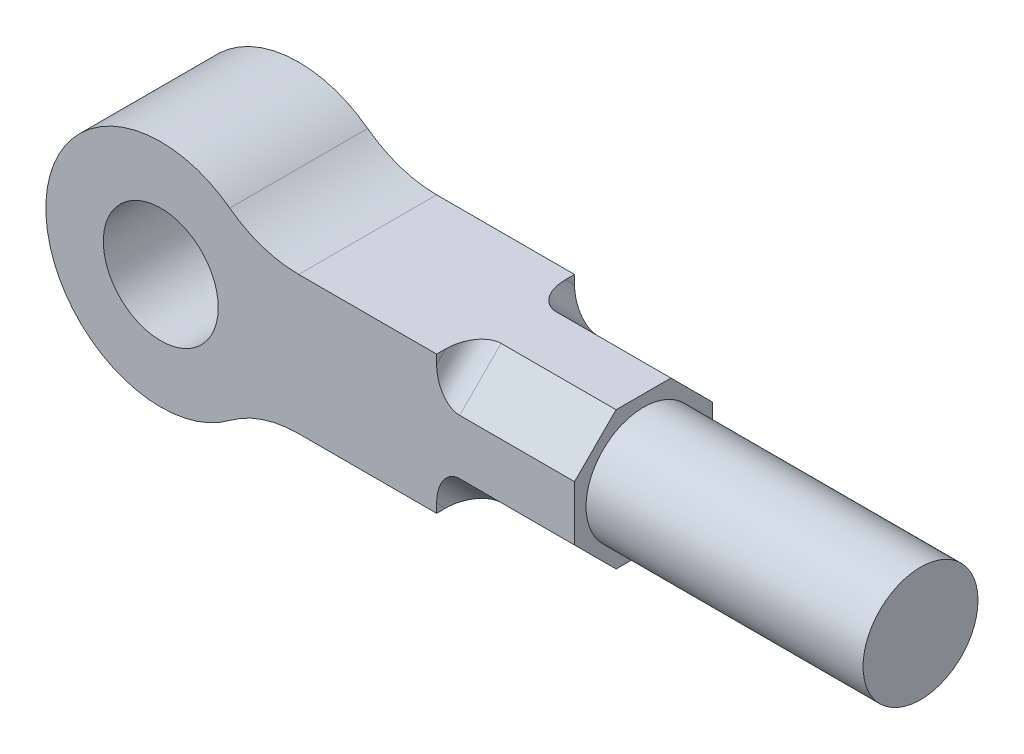
SolidWorks part; units mm, degrees
ref_plane "Front Plane" through (0, 0, 0) normal (0, 0, 1) x (1, 0, 0)
ref_plane "Top Plane" through (0, 0, 0) normal (0, 1, 0) x (1, 0, 0)
ref_plane "Right Plane" through (0, 0, 0) normal (1, 0, 0) x (0, 0, -1)
sketch "Sketch1" plane through (0, 0, 0) normal (0, 0, 1) x (1, 0, 0)
  line L0 (0, 0) -> (50000, 0) construction
  line L2 (60, 30) -> (180, 30)
  line L3 (60, -30) -> (180, -30)
  line L4 (180, 30) -> (180, -30)
  arc A0 (30, 40) -> (30, -40) centre (0, 0) ccw
  circle A1 centre (0, 0) radius 25
  arc A2 (30, -40) -> (60, -30) centre (60, -80) cw
  arc A3 (60, 30) -> (30, 40) centre (60, 80) cw
  point P13 (40, 30)
  dimension "D1" = 100
  dimension "D2" = 50
  dimension "D5" = 50
  dimension "D3" = 60
  dimension "D4" = 140
extrude "Boss-Extrude1" add sketch "Sketch1" along normal blind 60
sketch "Sketch2" plane through (180, 0, 0) normal (1, 0, 0) x (0, 0, -1)
  line L1 (-18.06, 30) -> (0, 11.94)
  line L2 (-60, 30) -> (0, 30) construction
  line L3 (0, -30) -> (0, 30) construction
  line L4 (0, -11.94) -> (-18.06, -30)
  line L5 (-41.94, -30) -> (-60, -11.94)
  line L6 (-60, 11.94) -> (-41.94, 30)
  circle A0 centre (-30, 0) radius 25
  point P19 (-30, 0)
  line M1 (0, -30) -> (0, 30)
  line M2 (0, 30) -> (-60, 30)
  line M3 (-60, 30) -> (-60, -30)
  line M4 (-60, -30) -> (0, -30)
  dimension "D1" = 50
  dimension "D2" = 30
  dimension "D3" = 18.06
  dimension "D4" = 18.06
  dimension "D5" = 4
extrude "Cut-Extrude1" cut sketch "Sketch2" against normal blind 60 contours L6 M3 M2 | L1 M2 M1 | L4 M1 M4 | L5 M4 M3 region at (180, 23.98, 6.02) region at (180, 23.98, 53.98) region at (180, -23.98, 6.02) region at (180, -23.98, 53.98)
extrude "Boss-Extrude2" add sketch "Sketch2<3>" along normal blind 120.5 contours A0 region at (180, 0, 30)
sketch "Sketch2<3>" plane through (180, 0, 0) normal (1, 0, 0) x (0, 0, -1) same geometry as "Sketch2"
fillet "Fillet1" radius 10 4 edges at (120, -20.97, 50.97) (120, -20.97, 9.03) (120, 20.97, 9.03) (120, 20.97, 50.97)
